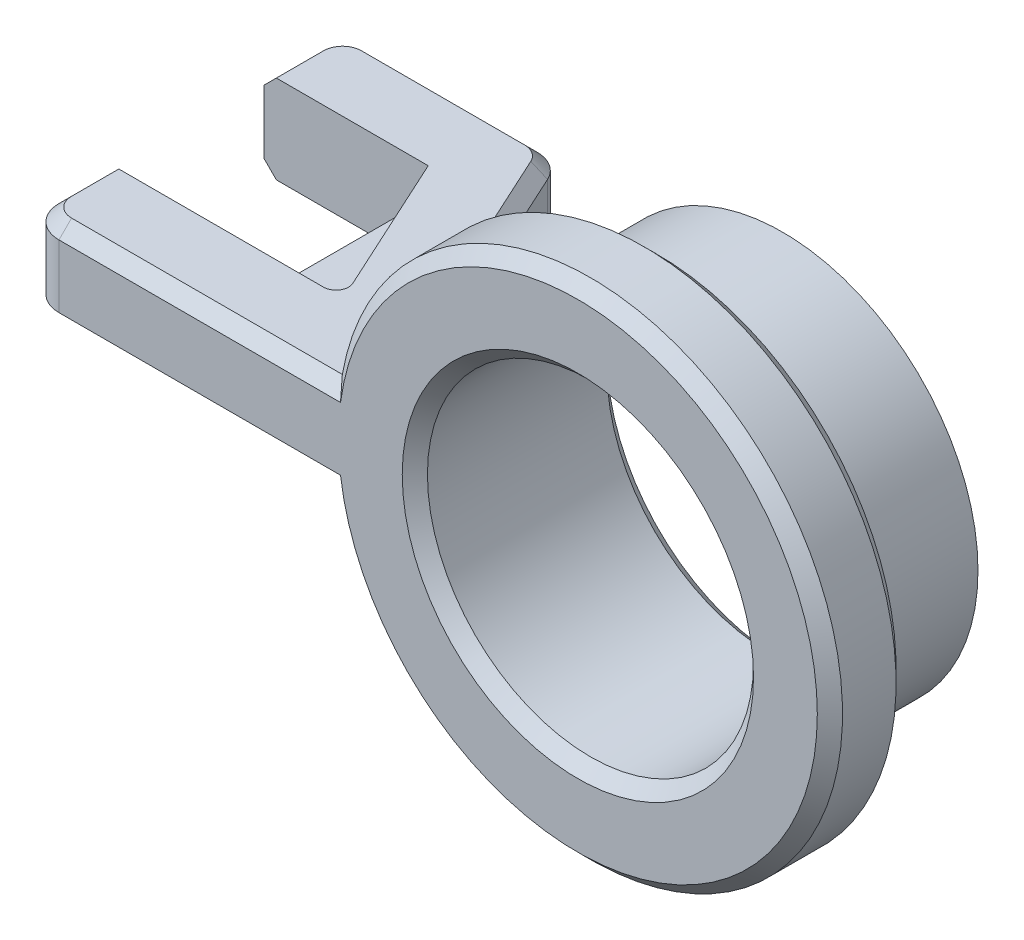
SolidWorks part; units mm, degrees
ref_plane "Front Plane" through (0, 0, 0) normal (0, 0, 1) x (1, 0, 0)
ref_plane "Top Plane" through (0, 0, 0) normal (0, 1, 0) x (1, 0, 0)
ref_plane "Right Plane" through (0, 0, 0) normal (1, 0, 0) x (0, 0, -1)
sketch "Sketch1" plane through (0, 0, 0) normal (0, 0, 1) x (1, 0, 0)
  circle A0 centre (0, 0) radius 8
  circle A1 centre (0, 0) radius 5.175
  dimension "D1" = 16
  dimension "D2" = 10.35
extrude "Boss-Extrude1" add sketch "Sketch1" along normal blind 2.5
sketch "Sketch2" plane through (0, 0, 0) normal (0, 0, -1) x (-1, 0, 0)
  circle A0 centre (0, 0) radius 5.175 construction
  circle A1 centre (0, 0) radius 5.175
  circle A2 centre (0, 0) radius 6.2
  dimension "D1" = 12.4
extrude "Boss-Extrude2" add sketch "Sketch2" along normal blind 4
chamfer "Chamfer1" distance 0.4 angle 45 4 edges at (-5.175, 0, -4) (5.175, 0, 2.5) (8, 0, 0) (8, 0, 2.5)
sketch "Sketch3" plane through (0, 0, 2.5) normal (0, 0, 1) x (1, 0, 0)
  line L0 (0, 0) -> (-13.7635, 0) construction
  line L2 (-17.4699, -1.4) -> (-7.4699, -1.4)
  line L3 (-17.4699, -1.4) -> (-17.4699, 1.4)
  line L4 (-17.4699, 1.4) -> (-7.4699, 1.4)
  line L5 (-7.4699, -1.4) -> (-7.4699, 1.4)
  line L6 (-17.4699, -1.4) -> (-7.4699, 1.4) construction
  line L7 (-17.4699, 1.4) -> (-7.4699, -1.4) construction
  circle A0 centre (0, 0) radius 7.6 construction
  point P3 (-12.4699, 0)
  point P10 (0, 0)
  dimension "D1" = 2.8
  dimension "D2" = 10
extrude "Boss-Extrude3" add sketch "Sketch3" against normal up to surface (2.5 mm away) up to face at (7.6, 0, 0)
sketch "Sketch4" plane through (0, 1.4, 0) normal (0, 1, 0) x (1, 0, 0)
  line L0 (-10.75, 31.5) -> (-10.75, -7.3651) construction
  line L1 (-17.75, 2.473) -> (-17.75, -5.0873) construction
  line L2 (-17.4699, 0) -> (-17.4699, 7.9979) construction
  line L3 (-17.4699, 7.5) -> (-10.6477, 7.5)
  line L4 (-10.6477, 7.5) -> (-7.2, 0)
  line L5 (-17.4699, 0) -> (-7.4699, 0) construction
  line L6 (-17.4699, 7.5) -> (-17.4699, 5)
  line L7 (-17.4699, 5) -> (-12.25, 5)
  line L8 (-12.25, 5) -> (-9.9515, 0)
  line L9 (-12.25, 12.1173) -> (-12.25, -4.2635) construction
  line L11 (-8.75, 31.5) -> (-8.75, -6.832) construction
  line L12 (0, 0) -> (0, 15.1221) construction
  line L13 (-7.2, 15.1221) -> (-7.2, -7.3651) construction
  line L14 (7.6, 0) -> (-7.4699, 0) construction
  line L15 (-9.9515, 0) -> (-7.2, 0)
  point P23 (0, 0)
  point P29 (-10.75, 31.5)
  point P30 (-8.9239, 3.75)
  point P31 (0, 0)
  point P32 (0, 0)
  point P33 (0, 0)
  point P34 (0, 0)
  dimension "D1" = 7
  dimension "D2" = 1.5
  dimension "D3" = 2.5
  dimension "D4" = 7.2
  dimension "D5" = 5
  dimension "D6" = 2.5
extrude "Boss-Extrude4" add sketch "Sketch4" against normal up to surface (2.8 mm away) up to face at (-10.9388, -1.4, 1.1833)
ref_plane "Plane1" through (0, -0.1, 0) normal (0, 1, 0) x (1, 0, 0)
sketch "Sketch5" plane through (0, -0.1, 0) normal (0, 1, 0) x (1, 0, 0)
  line L0 (-12.25, 5) -> (-12.25, 0)
  line L1 (-17.4699, 0) -> (-9.9515, 0) construction
  line L2 (-12.25, 0) -> (-9.9515, 0)
  line L3 (-9.9515, 0) -> (-12.25, 5)
extrude "Boss-Extrude5" add sketch "Sketch5" along normal blind 0.6 and the other way blind 0.6
fillet "Fillet1" radius 0.4 6 edges at (-9.9515, 0.95, 0) (-9.9515, -1.05, 0) (-11.1008, -0.7, 0) (-11.1008, -0.7, -2.5) (-11.1008, 0.5, -2.5) (-11.1008, 0.5, 0)
fillet "Fillet2" radius 1 3 edges at (-17.4699, 0, 2.5) (-17.4699, 0, -7.5) (-10.6477, 0, -7.5)
chamfer "Chamfer2" distance 0.4 angle 45 16 edges at (-17.4699, -1.4, -5.75) (-17.177, -1.4, -7.2071) (-13.8793, -1.4, -7.5) (-10.7491, -1.4, -7.3419) (-8.79, -1.4, -3.4588) (-17.4699, 1.4, -5.75) (-17.177, 1.4, -7.2071) (-13.8793, 1.4, -7.5) (-10.7491, 1.4, -7.3419) (-8.79, 1.4, -3.4588) (-17.4699, -1.4, 0.75) (-17.177, -1.4, 2.2071) (-11.9699, -1.4, 2.5) (-17.4699, 1.4, 0.75) (-17.177, 1.4, 2.2071) (-11.9699, 1.4, 2.5)
